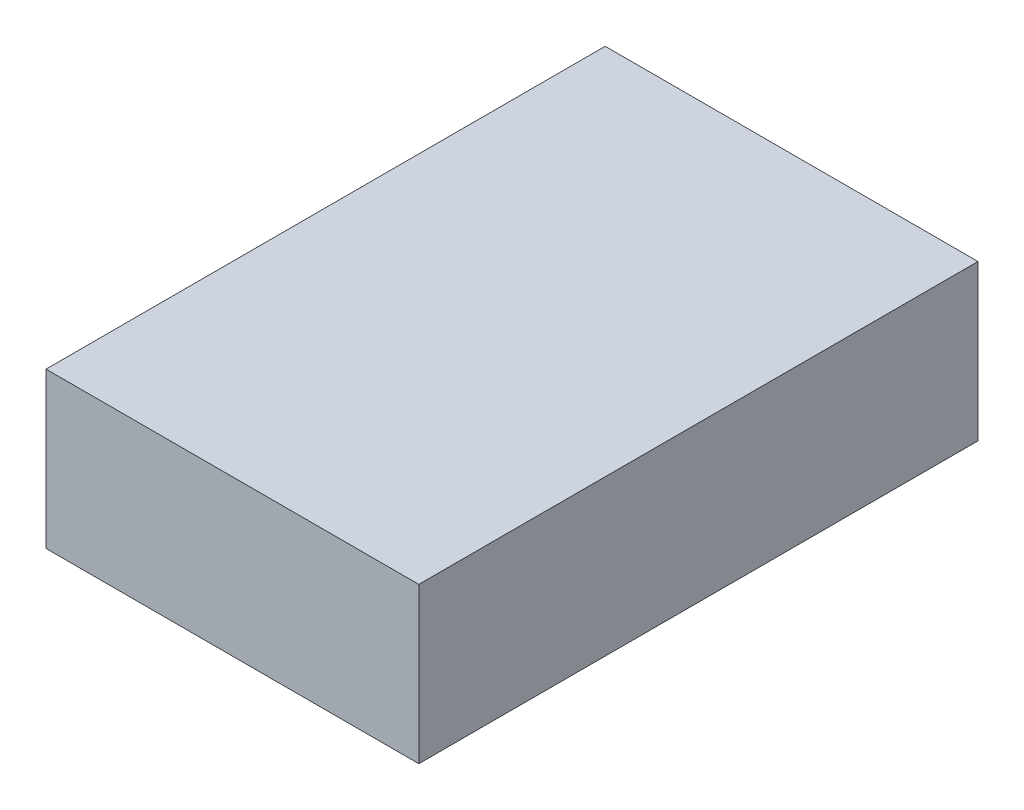
SolidWorks part; units mm, degrees
ref_plane "Front Plane" through (0, 0, 0) normal (0, 0, 1) x (1, 0, 0)
ref_plane "Top Plane" through (0, 0, 0) normal (0, 1, 0) x (1, 0, 0)
ref_plane "Right Plane" through (0, 0, 0) normal (1, 0, 0) x (0, 0, -1)
sketch "Sketch1" plane through (0, 0, 0) normal (0, 1, 0) x (1, 0, 0)
  line L1 (30, -45) -> (-30, -45)
  line L2 (30, -45) -> (30, 45)
  line L3 (30, 45) -> (-30, 45)
  line L4 (-30, -45) -> (-30, 45)
  line L5 (30, -45) -> (-30, 45) construction
  line L6 (30, 45) -> (-30, -45) construction
  point P0 (0, 0)
  dimension "D1" = 90
  dimension "D2" = 60
extrude "Boss-Extrude1" add sketch "Sketch1" along normal blind 25
sketch "wood" plane through (0, 25, 0) normal (0, 1, 0) x (1, 0, 0)
  line L0 (-30, 45) -> (-31.9, 45) construction
  dimension "wood_width" = 1.9
equation "\"wood_width\"= 1.9mm"
equation "\"wood_width@wood\"=\"wood_width\""
